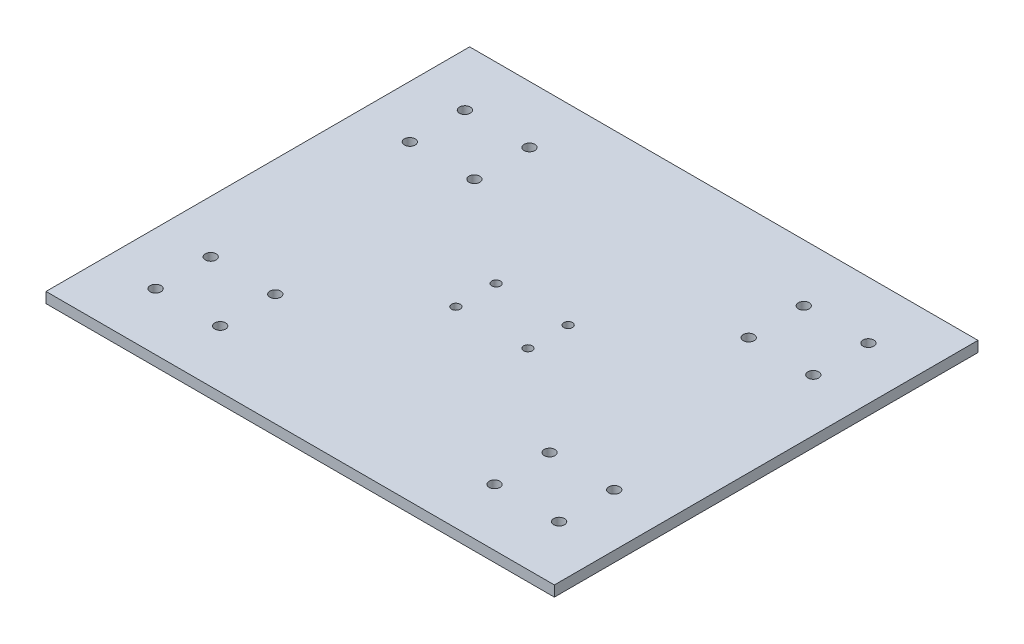
SolidWorks part; units mm, degrees
ref_plane "Front Plane" through (0, 0, 0) normal (0, 0, 1) x (1, 0, 0)
ref_plane "Top Plane" through (0, 0, 0) normal (0, 1, 0) x (1, 0, 0)
ref_plane "Right Plane" through (0, 0, 0) normal (1, 0, 0) x (0, 0, -1)
sketch "Sketch1" plane through (0, 0, 0) normal (0, 1, 0) x (1, 0, 0)
  line L1 (-120, -100) -> (120, -100)
  line L2 (-120, -100) -> (-120, 100)
  line L3 (-120, 100) -> (120, 100)
  line L4 (120, -100) -> (120, 100)
  line L5 (-120, -100) -> (120, 100) construction
  line L6 (-120, 100) -> (120, -100) construction
  point P0 (0, 0)
  dimension "D1" = 240
  dimension "D2" = 200
extrude "Boss-Extrude1" add sketch "Sketch1" along normal mid plane 5
sketch "Sketch2" plane through (0, 2.5, 0) normal (0, 1, 0) x (1, 0, 0)
  line L5 (-80, 100) -> (-80, -100)
  line L6 (-80, 100) -> (-80, -100) construction
  line L8 (80, -100) -> (80, 100)
  line L9 (80, -100) -> (80, 100) construction
  line L11 (120, 60) -> (-120, 60)
  line L12 (120, 60) -> (-120, 60) construction
  line L14 (-120, -60) -> (120, -60)
  line L15 (-120, -60) -> (120, -60) construction
  line L16 (-95.25, 73) -> (-64.75, 73) construction
  line L17 (-95.25, 73) -> (-95.25, 47) construction
  line L18 (-95.25, 47) -> (-64.75, 47) construction
  line L19 (-64.75, 73) -> (-64.75, 47) construction
  line L20 (-95.25, 73) -> (-64.75, 47) construction
  line L21 (-95.25, 47) -> (-64.75, 73) construction
  line L22 (64.75, 47) -> (95.25, 47) construction
  line L23 (64.75, 47) -> (64.75, 73) construction
  line L24 (64.75, 73) -> (95.25, 73) construction
  line L25 (95.25, 47) -> (95.25, 73) construction
  line L26 (64.75, 47) -> (95.25, 73) construction
  line L27 (64.75, 73) -> (95.25, 47) construction
  line L28 (64.75, -47) -> (95.25, -47) construction
  line L29 (64.75, -47) -> (64.75, -73) construction
  line L30 (64.75, -73) -> (95.25, -73) construction
  line L31 (95.25, -47) -> (95.25, -73) construction
  line L32 (64.75, -47) -> (95.25, -73) construction
  line L33 (64.75, -73) -> (95.25, -47) construction
  line L34 (-95.25, -73) -> (-64.75, -73) construction
  line L35 (-95.25, -73) -> (-95.25, -47) construction
  line L36 (-95.25, -47) -> (-64.75, -47) construction
  line L37 (-64.75, -73) -> (-64.75, -47) construction
  line L38 (-95.25, -73) -> (-64.75, -47) construction
  line L39 (-95.25, -47) -> (-64.75, -73) construction
  circle A0 centre (-95.25, 73) radius 2.55
  circle A1 centre (-95.25, 47) radius 2.55
  circle A2 centre (-64.75, 73) radius 2.55
  circle A3 centre (-64.75, 47) radius 2.55
  circle A4 centre (-95.25, -47) radius 2.55
  circle A5 centre (-95.25, -73) radius 2.55
  circle A6 centre (-64.75, -73) radius 2.55
  circle A7 centre (-64.75, -47) radius 2.55
  circle A8 centre (95.25, -47) radius 2.55
  circle A9 centre (64.75, -47) radius 2.55
  circle A10 centre (64.75, -73) radius 2.55
  circle A11 centre (95.25, -73) radius 2.55
  circle A12 centre (64.75, 73) radius 2.55
  circle A13 centre (64.75, 47) radius 2.55
  circle A14 centre (95.25, 73) radius 2.55
  circle A15 centre (95.25, 47) radius 2.55
  point P0 (-80, 60)
  point P13 (80, 60)
  point P18 (80, -60)
  point P23 (-80, -60)
  dimension "D13" = 5.1
  dimension "D14" = 5.1
  dimension "D15" = 5.1
  dimension "D16" = 5.1
  dimension "D17" = 5.1
  dimension "D18" = 5.1
  dimension "D19" = 5.1
  dimension "D20" = 5.1
  dimension "D21" = 5.1
  dimension "D22" = 5.1
  dimension "D23" = 5.1
  dimension "D24" = 5.1
  dimension "D25" = 5.1
  dimension "D26" = 5.1
  dimension "D27" = 5.1
  dimension "D28" = 5.1
  dimension "D1" = 40
  dimension "D5" = 30.5
  dimension "D6" = 26
  dimension "D7" = 30.5
  dimension "D8" = 26
  dimension "D9" = 26
  dimension "D10" = 30.5
  dimension "D11" = 26
  dimension "D12" = 30.5
  dimension "D2" = 40
  dimension "D3" = 40
  dimension "D4" = 40
extrude "Cut-Extrude1" cut sketch "Sketch2" against normal through all
sketch "Sketch3" plane through (0, 2.5, 0) normal (0, 1, 0) x (1, 0, 0)
  line L1 (-17, -9.5) -> (17, -9.5) construction
  line L2 (-17, -9.5) -> (-17, 9.5) construction
  line L3 (-17, 9.5) -> (17, 9.5) construction
  line L4 (17, -9.5) -> (17, 9.5) construction
  line L5 (-17, -9.5) -> (17, 9.5) construction
  line L6 (-17, 9.5) -> (17, -9.5) construction
  circle A0 centre (-17, 9.5) radius 2.05
  circle A1 centre (17, 9.5) radius 2.05
  circle A2 centre (17, -9.5) radius 2.05
  circle A3 centre (-17, -9.5) radius 2.05
  point P0 (0, 0)
  dimension "D3" = 4.1
  dimension "D4" = 4.1
  dimension "D5" = 4.1
  dimension "D6" = 4.1
  dimension "D1" = 34
  dimension "D2" = 19
extrude "Cut-Extrude2" cut sketch "Sketch3" against normal through all
